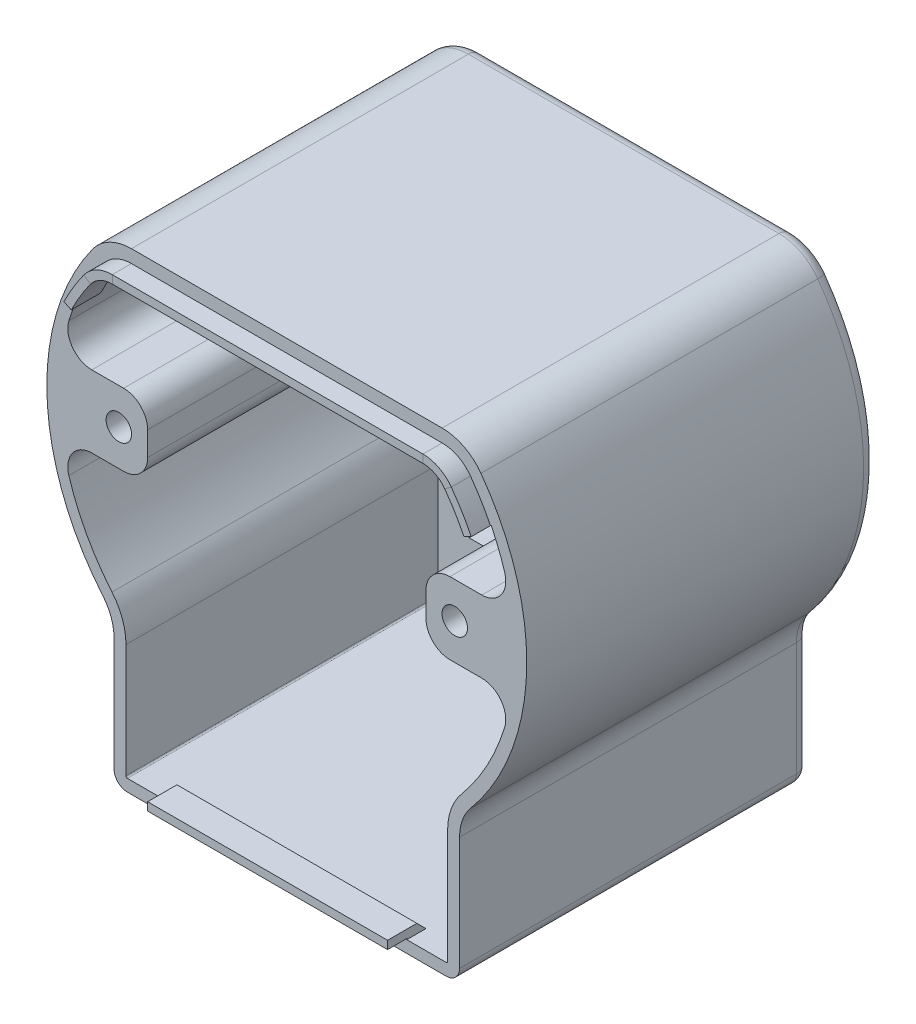
SolidWorks part; units mm, degrees
note: The reader was unsure of these and kept them because the rebuilt part matched: shared geometry of "Skizze6<2>", "Skizze9<4>".
ref_plane "Ebene vorne" through (0, 0, 0) normal (0, 0, 1) x (1, 0, 0)
ref_plane "Ebene oben" through (0, 0, 0) normal (0, 1, 0) x (1, 0, 0)
ref_plane "Ebene rechts" through (0, 0, 0) normal (1, 0, 0) x (0, 0, -1)
sketch "Skizze1" plane through (0, 0, 0) normal (0, 0, 1) x (1, 0, 0)
  line L0 (0, 15.499) -> (0, -28.3741) construction
  line L1 (0, 33.5) -> (-32.369, 33.5)
  line L2 (0, 33.5) -> (32.369, 33.5)
  line L3 (-36, -38.5227) -> (-36, -62.2)
  line L4 (-33.2, -65) -> (0, -65)
  line L5 (-50, 78.1636) -> (-50, -33.9451) construction
  line L6 (50, 78.1636) -> (50, -33.9451) construction
  line L7 (-50, 0) -> (50, 0) construction
  line L8 (36, -38.5227) -> (36, -62.2)
  line L10 (0, -65) -> (33.2, -65)
  arc A0 (-40.4612, 29.375) -> (-38.3333, -32.1023) centre (0, 0) ccw
  arc A3 (40.4612, 29.375) -> (38.3333, -32.1023) centre (0, 0) cw
  arc A8 (32.369, 33.5) -> (40.4612, 29.375) centre (32.369, 23.5) cw
  arc A9 (-32.369, 33.5) -> (-40.4612, 29.375) centre (-32.369, 23.5) ccw
  arc A10 (38.3333, -32.1023) -> (36, -38.5227) centre (46, -38.5227) ccw
  arc A11 (-38.3333, -32.1023) -> (-36, -38.5227) centre (-46, -38.5227) cw
  arc A12 (36, -62.2) -> (33.2, -65) centre (33.2, -62.2) cw
  arc A13 (-36, -62.2) -> (-33.2, -65) centre (-33.2, -62.2) ccw
  point P18 (0, 0)
  point P34 (36, -65)
  point P37 (-36, -65)
  dimension "D1" = 72
  dimension "D4" = 10
  dimension "D2" = 10
  dimension "D7" = 2.8
  dimension "D3" = 65
  dimension "D5" = 33.5
  dimension "D6" = 100
extrude "Linear-Austragen-Dünn1" add sketch "Skizze1" along normal blind 65 thin thin type one direction reverse wall 2.49
sketch "Skizze3" plane through (0, 0, 0) normal (0, 0, -1) x (-1, 0, 0)
  line L0 (36, -38.5227) -> (36, -62.2) construction
  line L1 (33.2, -65) -> (-33.2, -65) construction
  line L2 (-36, -62.2) -> (-36, -38.5227) construction
  line L3 (-32.369, 33.5) -> (32.369, 33.5) construction
  line L4 (36, -38.5227) -> (36, -62.2)
  line L5 (33.2, -65) -> (-33.2, -65)
  line L6 (-36, -62.2) -> (-36, -38.5227)
  line L7 (-32.369, 33.5) -> (32.369, 33.5)
  line L9 (-29.5, -29.5) -> (29.5, -29.5)
  line L10 (-29.5, -29.5) -> (-29.5, 29.5)
  line L11 (-29.5, 29.5) -> (29.5, 29.5)
  line L12 (29.5, -29.5) -> (29.5, 29.5)
  line L13 (-29.5, -29.5) -> (29.5, 29.5) construction
  line L14 (-29.5, 29.5) -> (29.5, -29.5) construction
  line L16 (0, 29.5) -> (0, -29.5) construction
  line L19 (-29.5, 0) -> (29.5, 0) construction
  line L29 (-27, -29.5) -> (27, -29.5)
  line L30 (-27, -29.5) -> (-27, -48.5)
  line L31 (-27, -48.5) -> (27, -48.5)
  line L32 (27, -29.5) -> (27, -48.5)
  line L33 (-27, -29.5) -> (27, -48.5) construction
  line L34 (-27, -48.5) -> (27, -29.5) construction
  arc A0 (38.3333, -32.1023) -> (36, -38.5227) centre (46, -38.5227) ccw construction
  arc A1 (33.2, -65) -> (36, -62.2) centre (33.2, -62.2) ccw construction
  arc A2 (-36, -62.2) -> (-33.2, -65) centre (-33.2, -62.2) ccw construction
  arc A3 (-36, -38.5227) -> (-38.3333, -32.1023) centre (-46, -38.5227) ccw construction
  arc A4 (-40.4612, 29.375) -> (-38.3333, -32.1023) centre (0, 0) ccw construction
  arc A5 (-32.369, 33.5) -> (-40.4612, 29.375) centre (-32.369, 23.5) ccw construction
  arc A6 (40.4612, 29.375) -> (32.369, 33.5) centre (32.369, 23.5) ccw construction
  arc A7 (38.3333, -32.1023) -> (40.4612, 29.375) centre (0, 0) ccw construction
  arc A8 (38.3333, -32.1023) -> (36, -38.5227) centre (46, -38.5227) ccw
  arc A9 (33.2, -65) -> (36, -62.2) centre (33.2, -62.2) ccw
  arc A10 (-36, -62.2) -> (-33.2, -65) centre (-33.2, -62.2) ccw
  arc A11 (-36, -38.5227) -> (-38.3333, -32.1023) centre (-46, -38.5227) ccw
  arc A12 (-40.4612, 29.375) -> (-38.3333, -32.1023) centre (0, 0) ccw
  arc A13 (-32.369, 33.5) -> (-40.4612, 29.375) centre (-32.369, 23.5) ccw
  arc A14 (40.4612, 29.375) -> (32.369, 33.5) centre (32.369, 23.5) ccw
  arc A15 (38.3333, -32.1023) -> (40.4612, 29.375) centre (0, 0) ccw
  point P13 (0, -39)
  point P31 (-26.9588, -51.8091)
  point P32 (22.7, -49.5)
  point P33 (0, 0)
  line M17 (32.369, 33.5) -> (-32.369, 33.5)
  arc M18 (-32.369, 33.5) -> (-40.4612, 29.375) centre (-32.369, 23.5) ccw
  arc M19 (-40.4612, 29.375) -> (-38.3333, -32.1023) centre (0, 0) ccw
  arc M20 (-38.3333, -32.1023) -> (-36, -38.5227) centre (-46, -38.5227) cw
  line M21 (-36, -38.5227) -> (-36, -62.2)
  arc M22 (-36, -62.2) -> (-33.2, -65) centre (-33.2, -62.2) ccw
  line M23 (-33.2, -65) -> (33.2, -65)
  arc M24 (33.2, -65) -> (36, -62.2) centre (33.2, -62.2) ccw
  line M25 (36, -62.2) -> (36, -38.5227)
  arc M26 (36, -38.5227) -> (38.3333, -32.1023) centre (46, -38.5227) cw
  arc M27 (38.3333, -32.1023) -> (40.4612, 29.375) centre (0, 0) ccw
  arc M28 (40.4612, 29.375) -> (32.369, 33.5) centre (32.369, 23.5) ccw
  line M29 (-32.369, 31.01) -> (32.369, 31.01)
  arc M30 (32.369, 31.01) -> (38.4462, 27.9121) centre (32.369, 23.5) cw
  arc M31 (38.4462, 27.9121) -> (36.4243, -30.5036) centre (0, 0) cw
  arc M32 (36.4243, -30.5036) -> (33.51, -38.5227) centre (46, -38.5227) ccw
  line M33 (33.51, -38.5227) -> (33.51, -62.2)
  arc M34 (33.51, -62.2) -> (33.2, -62.51) centre (33.2, -62.2) cw
  line M35 (33.2, -62.51) -> (-33.2, -62.51)
  arc M36 (-33.2, -62.51) -> (-33.51, -62.2) centre (-33.2, -62.2) cw
  line M37 (-33.51, -62.2) -> (-33.51, -38.5227)
  arc M38 (-33.51, -38.5227) -> (-36.4243, -30.5036) centre (-46, -38.5227) ccw
  arc M39 (-36.4243, -30.5036) -> (-38.4462, 27.9121) centre (0, 0) cw
  arc M40 (-38.4462, 27.9121) -> (-32.369, 31.01) centre (-32.369, 23.5) cw
  dimension "D2" = 19
  dimension "D1" = 59
  dimension "D3" = 54
extrude "Aufsatz-Linear austragen2" add sketch "Skizze3" along normal blind 8 contours L9 L32 L31 L30 L10 L11 L12 M29 M40 M39 M38 M37 M36 M35 M34 M33 M32 M31 M30 | M28 M17 M18 M19 M20 M21 M22 M23 M24 M25 M26 M27 M40 M29 M30 M31 M32 M33 M34 M35 M36 M37 M38 M39
sketch "Skizze6" plane through (0, 0, 0) normal (1, 0, 0) x (0, 0, -1)
  line L1 (0, -7.5) -> (-65, -7.5)
  line L2 (0, -7.5) -> (0, 7.5)
  line L3 (0, 7.5) -> (-65, 7.5)
  line L4 (-65, -7.5) -> (-65, 7.5)
  line L5 (-65, 27.9121) -> (-65, -30.5036) construction
  point P8 (0, 0)
  point P10 (0, 0)
  dimension "D1" = 15
extrude "Aufsatz-Linear austragen3" add sketch "Skizze6" along normal up to next from offset 29
extrude "Aufsatz-Linear austragen4" add sketch "Skizze6<2>" against normal up to next from offset 29 offset against normal yes
sketch "Skizze6<2>" plane through (0, 0, 0) normal (1, 0, 0) x (0, 0, -1) same geometry as "Skizze6"
sketch "Skizze7" plane through (0, 0, 65) normal (0, 0, 1) x (1, 0, 0)
  line L0 (0, 33.5) -> (0, -65) construction
  line L1 (32.369, 33.5) -> (-32.369, 33.5) construction
  line L2 (-33.2, -65) -> (33.2, -65) construction
  circle A0 centre (-35, 0) radius 2.65
  circle A1 centre (35, 0) radius 2.65
  dimension "D1" = 70
  dimension "D2" = 5.3
extrude "Schnitt-Linear austragen2" cut sketch "Skizze7" against normal up to next
sketch "Skizze8" plane through (0, 0, 65) normal (0, 0, 1) x (1, 0, 0)
  circle A0 centre (-35, 0) radius 4.5
  circle A1 centre (35, 0) radius 4.5
  dimension "D1" = 9
extrude "Schnitt-Linear austragen3" cut sketch "Skizze8" against normal up to next from offset 5 offset against normal yes
sketch "Skizze9" plane through (0, 0, 0) normal (1, 0, 0) x (0, 0, -1)
  line L0 (-65, 31.01) -> (-65, 30.81)
  line L1 (-65, 31.01) -> (-65, 27.9121) construction
  line L2 (-65, 30.81) -> (-69, 30.81)
  line L3 (-69, 30.81) -> (-69, 29.12)
  line L4 (-69, 29.12) -> (-62.89, 29.12)
  line L5 (-62.89, 29.12) -> (-60, 32.01)
  line L6 (-65, 31.01) -> (0, 31.01) construction
  line L8 (-32.5, 31.01) -> (-32.5, -62.51) construction
  line L9 (-65, -62.51) -> (0, -62.51) construction
  line L10 (-32.5, -15.75) -> (-65, -15.75) construction
  line L11 (-65, -7.5) -> (-65, -30.5036) construction
  line L18 (-65, 31.01) -> (-65, 32.01)
  line L19 (-65, 33.5) -> (-65, 29.375) construction
  line L20 (-65, 32.01) -> (-60, 32.01)
  line L21 (-65, -63.51) -> (-60, -63.51)
  line L22 (-65, -62.51) -> (-65, -63.51)
  line L23 (-62.89, -60.62) -> (-60, -63.51)
  line L24 (-69, -60.62) -> (-62.89, -60.62)
  line L25 (-69, -62.31) -> (-69, -60.62)
  line L26 (-65, -62.31) -> (-69, -62.31)
  line L27 (-65, -62.51) -> (-65, -62.31)
  dimension "D1" = 0.2
  dimension "D2" = 1.69
  dimension "D3" = 1
  dimension "D4" = 5
  dimension "D5" = 4
  dimension "D6" = 45
sketch "Skizze10" plane through (0, 0, 65) normal (0, 0, 1) x (1, 0, 0)
  line L2 (32.369, 31.01) -> (-32.369, 31.01) construction
  line L4 (0, 33.5) -> (0, -62.51) construction
  line L5 (32.369, 33.5) -> (-32.369, 33.5) construction
  line L6 (-33.2, -62.51) -> (33.2, -62.51) construction
  line L15 (32.369, 31.01) -> (-32.369, 31.01)
  line L16 (-68.7346, 21.01) -> (72.4368, 21.01) construction
  arc A11 (-38.4462, 27.9121) -> (-46.9143, 7.5) centre (0, 0) ccw construction
  arc A12 (-32.369, 31.01) -> (-38.4462, 27.9121) centre (-32.369, 23.5) ccw construction
  arc A13 (46.9143, 7.5) -> (38.4462, 27.9121) centre (0, 0) ccw construction
  arc A19 (38.4462, 27.9121) -> (32.369, 31.01) centre (32.369, 23.5) ccw construction
  arc A20 (-38.4462, 27.9121) -> (-42.612, 21.01) centre (0, 0) ccw
  arc A21 (-32.369, 31.01) -> (-38.4462, 27.9121) centre (-32.369, 23.5) ccw
  arc A22 (42.612, 21.01) -> (38.4462, 27.9121) centre (0, 0) ccw
  arc A23 (38.4462, 27.9121) -> (32.369, 31.01) centre (32.369, 23.5) ccw
  dimension "D1" = 10
sweep "Austragung12" add profiles "Skizze9" path "Skizze10"
extrude "Aufsatz-Linear austragen6" add sketch "Skizze9<4>" along normal mid plane 50 contours L23 L21 L22 L27 L26 L25 L24
sketch "Skizze9<4>" plane through (0, 0, 0) normal (1, 0, 0) x (0, 0, -1) same geometry as "Skizze9"
fillet "Verrundung1" radius 5 8 edges at (29, 7.5, 32.5) (29, -7.5, 32.5) (-29, -7.5, 32.5) (-29, 7.5, 32.5) (46.9143, 7.5, 32.5) (46.9143, -7.5, 32.5) (-46.9143, -7.5, 32.5) (-46.9143, 7.5, 32.5)
fillet "Verrundung3" radius 2.8 12 edges at (-36.9104, 32.4093, -8) (0, 33.5, -8) (36.9104, 32.4093, -8) (49.9701, -1.7296, -8) (36.6014, -35.1071, -8) (36, -50.3614, -8) (35.1799, -64.1799, -8) (0, -65, -8) (-35.1799, -64.1799, -8) (-36, -50.3614, -8) (-36.6014, -35.1071, -8) (-49.9701, -1.7296, -8)
